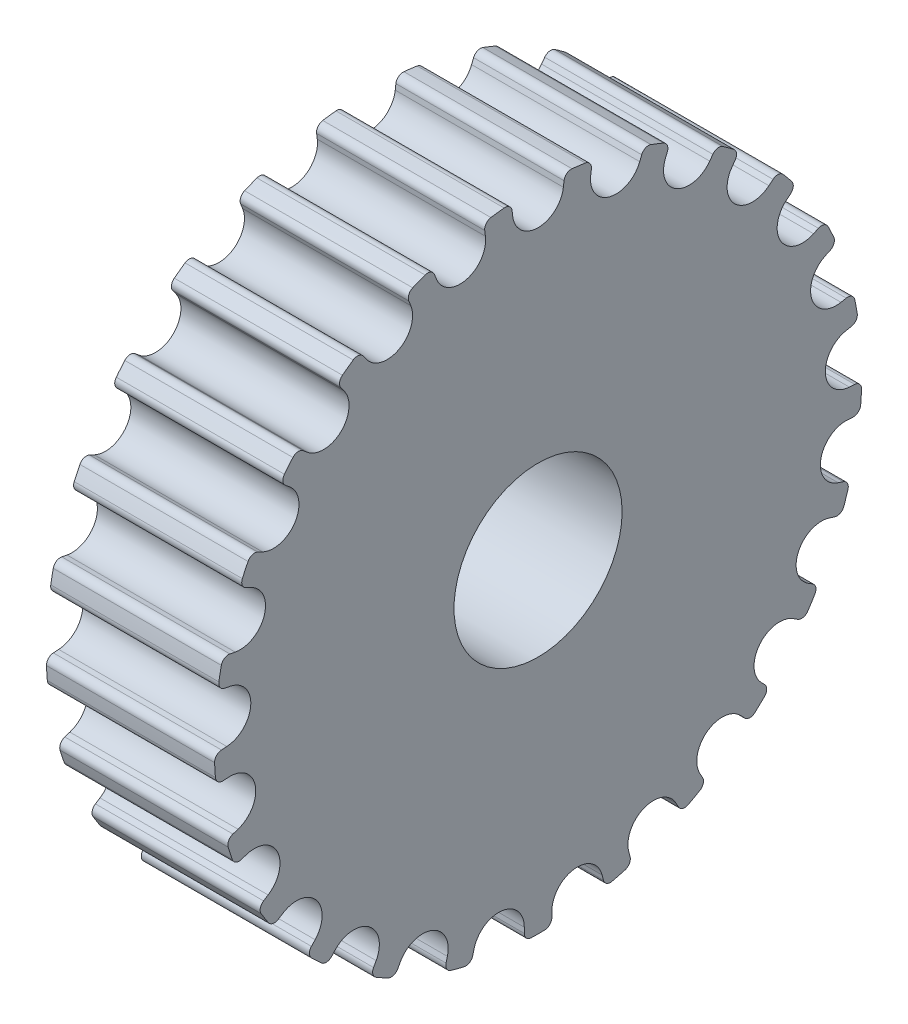
SolidWorks part; units mm, degrees
ref_plane "前视基准面" through (0, 0, 0) normal (0, 0, 1) x (1, 0, 0)
ref_plane "上视基准面" through (0, 0, 0) normal (0, 1, 0) x (1, 0, 0)
ref_plane "右视基准面" through (0, 0, 0) normal (1, 0, 0) x (0, 0, -1)
sketch "草图1" plane through (0, 0, 0) normal (0, 0, 1) x (1, 0, 0)
  line L0 (0, 0) -> (64.8368, 0) construction
  line L1 (0, 4.3416) -> (0, 11.554)
  line L2 (0, 11.554) -> (6, 11.554)
  line L3 (6, 11.554) -> (6, 8.6832)
  line L4 (6, 8.6832) -> (7.2, 8.6832)
  line L5 (7.2, 8.6832) -> (7.2, 4.3416)
  line L6 (7.2, 4.3416) -> (0, 4.3416)
  dimension "L" = 7.2
  dimension "B" = 6
  dimension "d" = 8.6832
  dimension "d1" = 17.3664
  dimension "da" = 23.108
revolve "旋转1" add sketch "草图1" angle 360 about L0
chamfer "倒角1" distance 1 angle 45 2 edges at (7.2, 0, 4.3416) (0, 0, 4.3416)
sketch "草图4" plane through (0, 0, 0) normal (-1, 0, 0) x (0, 0, 1)
  line L1 (-1.5, 4.0742) -> (1.5, 4.0742)
  line L2 (-1.5, 4.0742) -> (-1.5, 5.4742)
  line L3 (-1.5, 5.4742) -> (1.5, 5.4742)
  line L4 (1.5, 4.0742) -> (1.5, 5.4742)
  circle A0 centre (0, 0) radius 4.3416 construction
  dimension "键槽宽度" = 3
  dimension "t1" = 1.4
extrude "切除-拉伸1" cut sketch "草图4" against normal through all
ref_axis "基准轴1" through (-1.4, 0, 0) along (1, 0, 0)
sketch "草图6" plane through (0, 0, 0) normal (1, 0, 0) x (0, 0, -1)
  line L0 (0, 0) -> (0, 30.6512) construction
  line L1 (0.9266, 11.2634) -> (0.9032, 11.0731)
  line L2 (1.4702, 11.4601) -> (1.6668, 13.0617)
  line L3 (-1.4702, 11.4601) -> (-1.6668, 13.0617)
  line L4 (-0.9266, 11.2634) -> (-0.9032, 11.0731)
  circle A0 centre (0, 0) radius 11.554 construction
  circle A1 centre (0, 0) radius 10.274 construction
  arc A2 (-0.9032, 11.0731) -> (0.9032, 11.0731) centre (0, 11.184) ccw
  arc A3 (1.6668, 13.0617) -> (-1.6668, 13.0617) centre (0, 0) ccw
  arc A4 (0.9266, 11.2634) -> (1.2119, 11.4903) centre (1.1846, 11.2317) cw
  arc A5 (1.2119, 11.4903) -> (1.4702, 11.4601) centre (0, 0) cw
  arc A6 (-1.2119, 11.4903) -> (-1.4702, 11.4601) centre (0, 0) ccw
  arc A7 (-0.9266, 11.2634) -> (-1.2119, 11.4903) centre (-1.1846, 11.2317) ccw
  point P7 (0, 1.9)
  point P8 (0, 29.3712)
  point P15 (0.9574, 11.5143)
  dimension "D1" = 20.548
  dimension "ra" = 0.26
  dimension "rf" = 0.91
  dimension "hg" = 1.28
  dimension "D3" = 0.26
  dimension "D4" = 1.6136
  dimension "angle" = 14
  dimension "bw" = 1.9
extrude "切除-拉伸2" cut sketch "草图6" along normal up to next
pattern_circular "阵列(圆周)3" count 25 over 360 about axis through (-1.4, 0, 0) along (1, 0, 0) of "切除-拉伸2"
sketch "草图7" plane through (7.2, 0, 0) normal (1, 0, 0) x (0, 0, -1)
  circle A0 centre (0, 0) radius 13
  dimension "D1" = 26
extrude "切除-拉伸3" cut sketch "草图7" against normal offset from surface (1.2 mm away) 6 up to face at (0, 2.6834, 0)
sketch "草图8" plane through (0, 0, 0) normal (-1, 0, 0) x (0, 0, 1)
  circle A0 centre (0, 0) radius 6.5
  dimension "D1" = 13
extrude "凸台-拉伸1" add sketch "草图8" against normal up to surface (6 mm away) up to face at (6, 0, 0)
sketch "草图9" plane through (6, 0, 0) normal (1, 0, 0) x (0, 0, -1)
  circle A0 centre (0, 0) radius 3
  dimension "D1" = 6
extrude "切除-拉伸4" cut sketch "草图9" against normal up to surface (6 mm away) up to face at (0, 0, 0)
equation "\"D1@草图6\" = \"da@草图1\"  - \"hg@草图6\" - \"hg@草图6\""
equation "\"D3@草图6\" = \"ra@草图6\""
